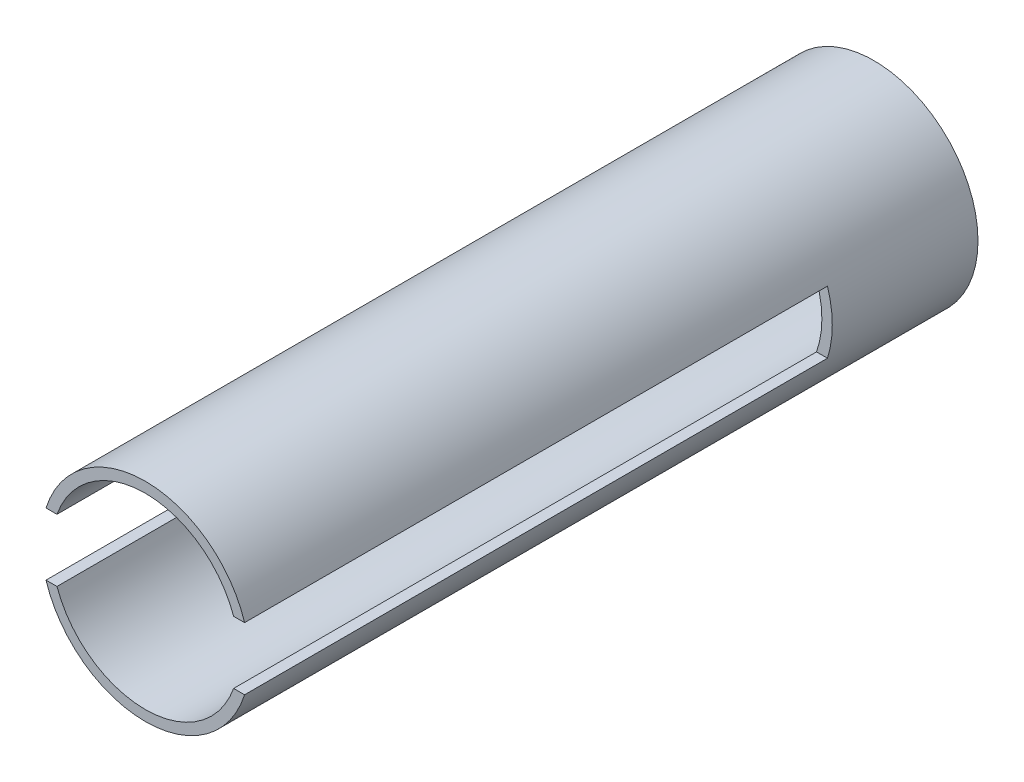
SolidWorks part; units mm, degrees
ref_plane "Front Plane" through (0, 0, 0) normal (0, 0, 1) x (1, 0, 0)
ref_plane "Top Plane" through (0, 0, 0) normal (0, 1, 0) x (1, 0, 0)
ref_plane "Right Plane" through (0, 0, 0) normal (1, 0, 0) x (0, 0, -1)
sketch "Sketch1" plane through (0, 0, 0) normal (0, 0, 1) x (1, 0, 0)
  line L1 (-88.9, -19.05) -> (88.9, -19.05)
  line L2 (-88.9, -19.05) -> (-88.9, 19.05) construction
  line L3 (-88.9, 19.05) -> (88.9, 19.05)
  line L4 (88.9, -19.05) -> (88.9, 19.05) construction
  line L5 (-88.9, -19.05) -> (88.9, 19.05) construction
  line L6 (-88.9, 19.05) -> (88.9, -19.05) construction
  circle A0 centre (0, 0) radius 63.5
  circle A1 centre (0, 0) radius 57.15
  dimension "D1" = 127
  dimension "D4" = 6.35
  dimension "D2" = 38.1
  dimension "D3" = 177.8
extrude "Boss-Extrude1" add sketch "Sketch1" along normal mid plane 355.6 contours A1 L3 A0 | A1 L1 A0 region at (-57.2283, -20.3405, 0) region at (0, 62.2095, 0)
sketch "Sketch2" plane through (0, 0, -177.8) normal (0, 0, -1) x (-1, 0, 0)
  circle A0 centre (0, 0) radius 63.5 construction
  circle A1 centre (0, 0) radius 57.15 construction
  circle A2 centre (0, 0) radius 63.5
  circle A3 centre (0, 0) radius 57.15
extrude "Boss-Extrude2" add sketch "Sketch2" along normal blind 88.9
